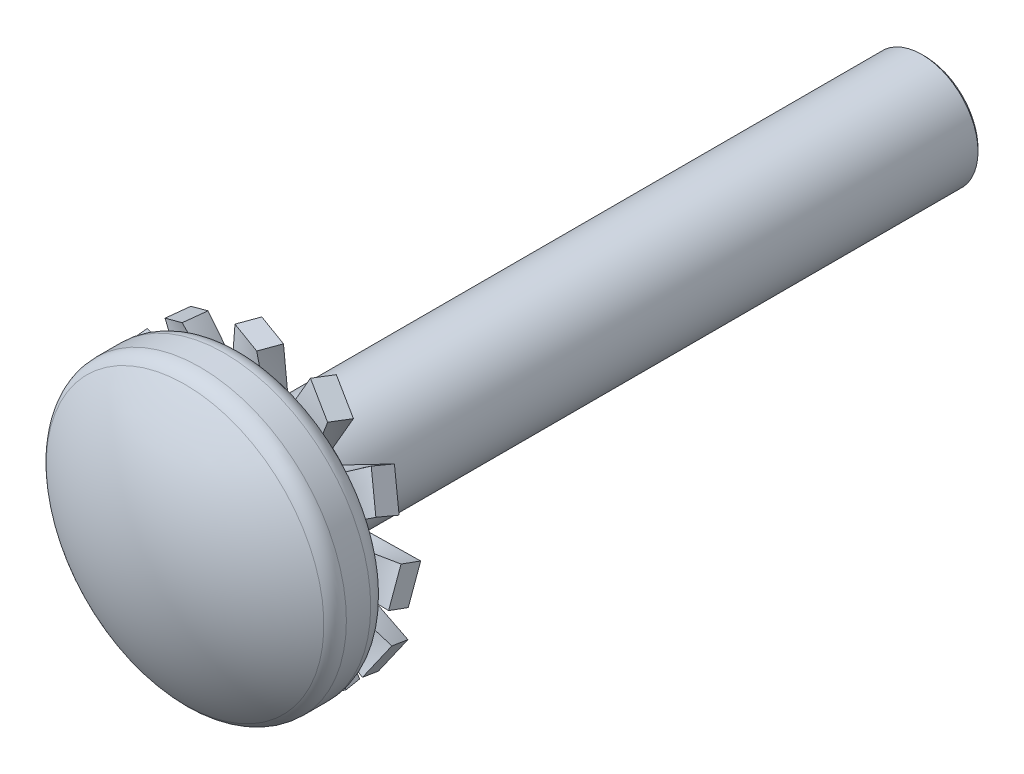
SolidWorks part; units mm, degrees
material "AISI 304"
ref_plane "Front Plane" through (0, 0, 0) normal (0, 0, 1) x (1, 0, 0)
ref_plane "Top Plane" through (0, 0, 0) normal (0, 1, 0) x (1, 0, 0)
ref_plane "Right Plane" through (0, 0, 0) normal (1, 0, 0) x (0, 0, -1)
sketch "Sketch1" plane through (0, 0, 0) normal (0, 0, 1) x (1, 0, 0)
  circle A0 centre (0, 0) radius 2.0828
  dimension "decimal equ" = 4.1656
curve "Helix/Spiral1" pitch 0.7937 height 19.8438 turns 25 parameters "helix length"=19.8438, "pitch"=0.7937
sketch "Sketch2" plane through (0, 0, 0) normal (1, 0, 0) x (0, 0, -1)
  line L0 (0.2977, 2.0828) -> (0.3969, 2.0828)
  line L1 (0.3969, 2.0828) -> (0.6945, 1.5672)
  line L2 (0.2977, 2.0828) -> (0, 1.5672)
  line L3 (0, 1.5672) -> (0.6945, 1.5672)
  line L4 (0.3473, 2.0828) -> (0.3473, 1.5672) construction
  line L6 (0.1488, 1.825) -> (0.5457, 1.825) construction
  line L7 (0, 1.5672) -> (0, 2.0828) construction
  line L8 (0, 2.0828) -> (0, -2.0828) construction
  line L9 (0, 2.0828) -> (0, -2.0828) construction
  point P8 (-3.2742, -2.0828)
  dimension "D1" = 60
  dimension "D3" = 0.0992
  dimension "D4" = 0.3969
  dimension "D2" = 3.2742
sketch "Sketch3" plane through (0, 0, 0) normal (1, 0, 0) x (0, 0, -1)
  line L0 (0, 0) -> (-19.05, 0) construction
  line L1 (0, 1.5672) -> (0.6945, 1.5672) construction
  line L2 (0, 0) -> (-19.05, 0)
  line L3 (0, 0) -> (0, 1.5672)
  line L4 (0, 1.5672) -> (-19.05, 1.5672)
  line L5 (-19.05, 0) -> (-19.05, 1.5672)
  dimension "length" = 19.05
revolve "Revolve1" add sketch "Sketch3" angle 360 about L0
sweep "Sweep1" [suppressed] add profiles "Sketch2" path "Helix/Spiral1"
sketch "Sketch39" plane through (0, 0, 0) normal (0, 0, -1) x (-1, 0, 0)
  circle A0 centre (0, 0) radius 2.0828 construction
  circle A1 centre (0, 0) radius 2.0828
extrude "Extrude5" [suppressed] cut sketch "Sketch39" along normal through all
sketch "Sketch38" plane through (0, 0, 0) normal (0, 0, -1) x (-1, 0, 0)
  circle A2 centre (0, 0) radius 1.4875
  circle A3 centre (0, 0) radius 1.4875
extrude "Extrude6" cut sketch "Sketch38" against normal through all draft 45 flip side to cut
sketch "Sketch10" plane through (0, 0, 0) normal (1, 0, 0) x (0, 0, -1)
  line L0 (0, 0) -> (23.0169, 0) construction
  line L1 (-273.05, 12.7) -> (-19.05, 12.7)
  line L2 (-273.05, 12.7) -> (-273.05, 0)
  line L3 (-273.05, 0) -> (-19.05, 0)
  line L4 (-19.05, 12.7) -> (-19.05, 0)
  line L5 (-19.05, 0) -> (-19.05, 1.5672) construction
  dimension "D1" = 254
  dimension "D2" = 12.7
revolve "Cut-Revolve2" [suppressed] cut sketch "Sketch10" angle 360 about L0
sketch "Sketch41" plane through (0, 0, 0) normal (1, 0, 0) x (0, 0, -1)
  line L0 (-19.05, 2.0828) -> (-19.05, 1.5672)
  line L1 (-19.05, 1.5672) -> (-18.1737, 1.5672)
  line L2 (-18.1737, 1.5672) -> (-17.6581, 2.0828)
  line L3 (-19.05, 2.0828) -> (-17.6581, 2.0828)
  line L4 (0, 1.5672) -> (0.6945, 1.5672) construction
  dimension "D1" = 0.8763
  dimension "D2" = 45
revolve "Cut-Revolve4" [suppressed] cut sketch "Sketch41" angle 360 about L2
sketch "Sketch8" plane through (0, 0, 0) normal (1, 0, 0) x (0, 0, -1)
  line L0 (0, 0) -> (-6.2449, 0) construction
  line L1 (-21.971, 0) -> (-19.05, 0)
  line L2 (-21.971, 0) -> (-21.971, 4.0894)
  line L3 (-21.971, 4.0894) -> (-19.05, 4.0894)
  line L4 (-19.05, 0) -> (-19.05, 4.0894)
  line L5 (-21.971, -4.0894) -> (-19.05, -4.0894) construction
  line L6 (-19.05, 0) -> (-19.05, 1.5672) construction
  dimension "head dia" = 8.1788
  dimension "head height" = 2.921
revolve "Revolve2" add sketch "Sketch8" angle 360 about L0
sketch "Sketch11" plane through (0, 0, 0) normal (1, 0, 0) x (0, 0, -1)
  line L0 (-20.5105, 4.0894) -> (-20.5105, -4.0894) construction
  line L1 (-21.971, 0) -> (-6.8951, 0) construction
  line L2 (-21.971, 4.0894) -> (-19.05, 4.0894) construction
  line L3 (-21.971, 0) -> (-21.971, 4.0894) construction
  line L4 (-20.2549, 4.0894) -> (-19.5758, 4.0894)
  line L6 (-19.05, 0) -> (-19.05, 4.0894) construction
  line L7 (-19.05, 3.5636) -> (-18.415, 3.5636)
  line L8 (-18.415, 3.5636) -> (-18.415, 4.7244)
  line L9 (-18.415, 4.7244) -> (-22.606, 4.7244)
  line L10 (-22.606, 4.7244) -> (-22.606, 0)
  line L11 (-22.606, 0) -> (-21.971, 0)
  arc A0 (-20.6751, 3.8796) -> (-21.971, 0) centre (-15.5156, 0) ccw
  arc A1 (-19.05, 3.5636) -> (-19.5758, 4.0894) centre (-19.5758, 3.5636) ccw
  arc A2 (-20.6751, 3.8796) -> (-20.2549, 4.0894) centre (-20.2549, 3.5636) cw
  dimension "D1" = 0.5258
  dimension "D2" = 0.635
  dimension "D3" = 0.635
  dimension "D4" = 0.635
revolve "Cut-Revolve3" cut sketch "Sketch11" angle 360 about L1
ref_plane "Plane1" through (0, 0, 21.971) normal (0, 0, 1) x (1, 0, 0)
sketch "Sketch12" plane through (0, 0, 21.971) normal (0, 0, 1) x (1, 0, 0)
  line L0 (0.508, 2.3264) -> (0.508, 1.1906)
  line L1 (0.508, 1.1906) -> (1.1906, 0.508) construction
  line L2 (1.1906, 0.508) -> (2.3264, 0.508)
  line L3 (0, 2.3813) -> (0, 0)
  line L4 (0, 0) -> (2.3813, 0)
  line L5 (0, 0) -> (0, 4.0894) construction
  line L6 (0, 0) -> (0.8493, 0.8493) construction
  line L7 (1.1906, 0) -> (1.1906, 1.5633) construction
  line L8 (0.508, 1.1906) -> (0.7079, 0.7079)
  line L9 (1.1906, 0.508) -> (0.7079, 0.7079)
  line L10 (0, 0) -> (0, -1.0114) construction
  line L11 (-0.508, 2.3264) -> (-0.508, 1.1906) construction
  arc A0 (2.3813, 0) -> (2.3264, 0.508) centre (0, 0) ccw
  arc A1 (0.508, 2.3264) -> (0, 2.3813) centre (0, 0) ccw
  arc A2 (-2.3813, 0) -> (-2.3264, 0.508) centre (0, 0) cw construction
  dimension "phillips dia" = 4.7625
  dimension "D2" = 45
  dimension "D4" = 22.5
  dimension "slot width" = 1.016
extrude "Cut-Extrude1" [suppressed] cut sketch "Sketch12" against normal blind 2.4829
draft "Draft3" [suppressed] type of draft neutral plane draft angle 15 neutral plane "Plane1" faces to draft 2 parameters "D1"=15
draft "Draft4" [suppressed] type of draft neutral plane draft angle 5 neutral plane "Plane1" faces to draft 4 parameters "D1"=5
pattern_circular "CirPattern1" [suppressed] count 4 over 360 about axis through (0, 0, 21.971) along (0, 0, -1) of bodies 110
ref_plane "Plane8" through (0, 0, 18.8939) normal (0, 0, -1) x (-1, 0, 0)
sketch "Sketch18" plane through (0, 0, 18.8939) normal (0, 0, 1) x (1, 0, 0)
  line L0 (0, 0) -> (0, 4.064) construction
  line L1 (1.5672, 0) -> (4.064, 0) construction
  circle A0 centre (0, 0) radius 4.064
  circle A1 centre (0, 0) radius 1.5672 construction
  circle A2 centre (0, 0) radius 1.5672 construction
  circle A3 centre (0, 0) radius 2.6908
  circle A4 centre (0, 0) radius 2.0828 construction
  point P8 (2.6908, 0)
  point P10 (0, 2.6908)
  dimension "washer dia." = 8.128
  dimension "D2" = 1.1235
sketch "Sketch21" plane through (0, 0, 18.8939) normal (0, 0, 1) x (1, 0, 0)
  circle A0 centre (0, 0) radius 2.6908
  circle A1 centre (0, 0) radius 1.5672
  circle A2 centre (0, 0) radius 2.0828 construction
extrude "Extrude2" add sketch "Sketch21" against normal blind 0.5842 separate body
ref_plane "Plane9" through (0, 2.6908, 0) normal (0, 1, 0) x (-1, 0, 0)
sketch "Sketch31" plane through (0, 2.6908, 0) normal (0, 1, 0) x (-1, 0, 0)
  line L1 (-0.508, 18.8939) -> (0.508, 18.8939)
  line L2 (-0.508, 18.8939) -> (-0.508, 18.3097)
  line L3 (-0.508, 18.3097) -> (0.508, 18.3097)
  line L4 (0.508, 18.8939) -> (0.508, 18.3097)
  line L5 (-2.6908, 18.3097) -> (2.6908, 18.3097) construction
  line L6 (0, 0) -> (0, 18.8939) construction
  line L7 (0.508, 18.6018) -> (-0.508, 18.6018) construction
  line L8 (0, 18.8939) -> (0, 18.3097) construction
  line L9 (2.6908, 18.8939) -> (-2.6908, 18.8939) construction
  dimension "D1" = 1.016
ref_plane "Plane10" through (0, 4.064, 0) normal (0, 1, 0) x (-1, 0, 0)
sketch "Sketch32" plane through (0, 4.064, 0) normal (0, 1, 0) x (-1, 0, 0)
  line L0 (-0.3775, 19.05) -> (-0.5773, 18.501)
  line L1 (-0.3775, 19.05) -> (0.5773, 18.7025)
  line L2 (-0.5773, 18.501) -> (0.3775, 18.1535)
  line L3 (0.5773, 18.7025) -> (0.3775, 18.1535)
  line L4 (-0.508, 18.8939) -> (-0.508, 18.3097) construction
  line L5 (-0.508, 18.3097) -> (0.508, 18.3097) construction
  line L6 (0.0999, 18.8763) -> (0, 18.6018) construction
  line L7 (0, 18.6018) -> (0.4774, 18.428) construction
  line L8 (0.508, 18.6018) -> (-0.508, 18.6018) construction
  line L9 (0, 0) -> (0, 6.2449) construction
  line L10 (-1.5672, 18.3097) -> (1.5672, 18.3097) construction
  dimension "D1" = 20
sketch "Sketch33" plane through (0, 2.6908, 0) normal (0, 1, 0) x (-1, 0, 0)
  line L1 (1.5672, 18.8939) -> (-1.5672, 18.8939) construction
  line L4 (0.508, 18.8939) -> (-0.508, 18.8939)
  line L5 (0.508, 18.3097) -> (0.508, 18.8939)
  line L6 (-0.508, 18.3097) -> (0.508, 18.3097)
  line L7 (-0.508, 18.8939) -> (-0.508, 18.3097)
  line L8 (0.508, 18.8939) -> (-0.508, 18.8939)
  line L9 (0.508, 18.3097) -> (0.508, 18.8939)
  line L10 (-0.508, 18.3097) -> (0.508, 18.3097)
  line L11 (-0.508, 18.8939) -> (-0.508, 18.3097)
  dimension "D1" = 0
extrude "Extrude3" add sketch "Sketch33" against normal up to next (1.1235 mm away)
loft "Loft2" add profiles "Sketch32", "Sketch31" connector at (0.3775, 4.064, 19.05) connector at (0.508, 2.6908, 18.8939)
pattern_circular "CirPattern4" count 12 over 360 about axis through (0, 0, 18.3097) along (0, 0, 1) of "Loft2", "Extrude3"
sketch "Sketch40" plane through (0, 0, 0) normal (1, 0, 0) x (0, 0, -1)
  line L0 (-18.8939, 4.064) -> (-18.3097, 4.064) construction
  line L1 (-18.8939, -4.064) -> (-18.3097, -4.064) construction
  line L2 (-18.6018, 4.064) -> (-18.6018, -4.064) construction
  line L3 (-18.6018, 0) -> (0, 0) construction
  line L4 (0, -1.4875) -> (0, 1.4875) construction
  line L6 (-18.8939, -5.9931) -> (-18.8939, 5.9931) construction
  dimension "D1" = 0.5842
  dimension "D2" = 8.128
equation "\"D3@Sketch2\" = \"pitch@Helix/Spiral1\"*.125"
equation "\"D4@Sketch2\" = \"pitch@Helix/Spiral1\"*.5"
equation "\"D1@Sketch11\" = \"head height@Sketch8\"*.18"
equation "\"D1@Cut-Extrude1\" = \"head height@Sketch8\"*.85"
equation "\"D1@Sketch31\" = \"washer dia.@Sketch18\"*.125"
equation "\"helix length@Helix/Spiral1\" = \"length@Sketch3\" + \"pitch@Helix/Spiral1\""
equation "\"D1@Sketch38\" = \"pitch@Helix/Spiral1\"*.750"
equation "\"D1@Plane8\" = \"D2@Sketch32\""
equation "\"D2@Sketch18\" = \"D1@Sketch18\"*.45"
equation "\"D2@Sketch2\" = \"pitch@Helix/Spiral1\"*4.125"
equation "\"D1@Sketch40\" = \"washer width@Extrude2\""
equation "\"D2@Sketch40\" = \"washer dia.@Sketch18\""
equation "\"D1@Sketch41\" = \"washer width@Extrude2\"*1.50"
